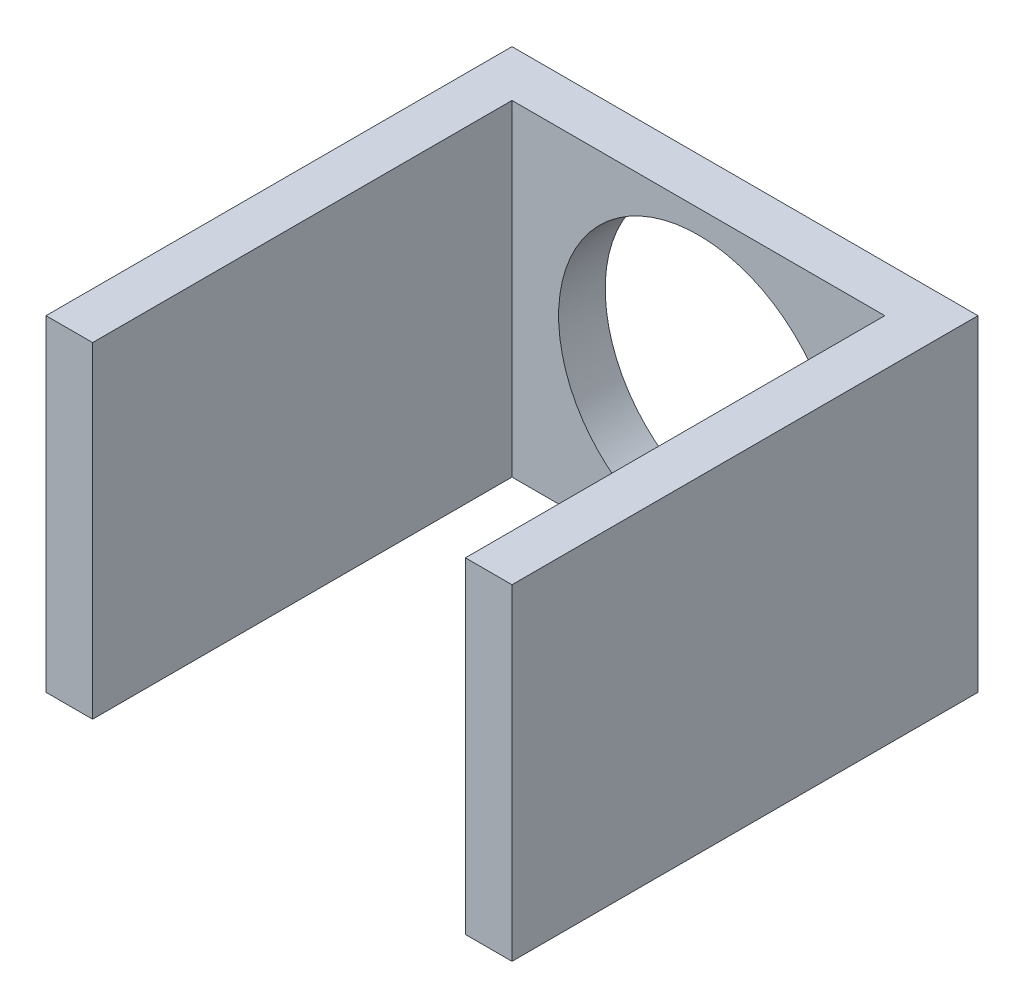
SolidWorks part; units mm, degrees
ref_plane "Plan de face" through (0, 0, 0) normal (0, 0, 1) x (1, 0, 0)
ref_plane "Plan de dessus" through (0, 0, 0) normal (0, 1, 0) x (1, 0, 0)
ref_plane "Plan de droite" through (0, 0, 0) normal (1, 0, 0) x (0, 0, -1)
sketch "Esquisse1" plane through (0, 0, 0) normal (0, 0, 1) x (1, 0, 0)
  line L0 (-90, 70) -> (-90, 0)
  line L1 (0, 0) -> (-100, 0)
  line L2 (0, 0) -> (0, 70)
  line L3 (0, 70) -> (-100, 70)
  line L4 (-100, 0) -> (-100, 70)
  line L5 (-10, 70) -> (-10, 0)
  dimension "D1" = 10
  dimension "D2" = 10
  dimension "D3" = 100
  dimension "D4" = 70
sketch "Esquisse4" plane through (0, 0, 0) normal (0, 0, 1) x (1, 0, 0)
  line L0 (-10, 70) -> (-10, 0) construction
  line L1 (-90, 70) -> (-90, 0) construction
  line L2 (0, 70) -> (-100, 70) construction
  line L3 (0, 0) -> (-100, 0) construction
  circle A0 centre (-50, 35) radius 30
  point P0 (-50, 35)
  dimension "D1" = 40
  dimension "D2" = 40
  dimension "D3" = 35
  dimension "D4" = 35
extrude "Boss.-Extru.2" add sketch "Esquisse1" along normal blind 10 contours L5 L3 L0 L1 region at (-50, 35, 0)
extrude "Boss.-Extru.3" add sketch "Esquisse1<4>" along normal blind 100 contours L3 L5 L1 L2 | L4 L1 L0 L3 region at (-95, 35, 0) region at (-5, 35, 0)
sketch "Esquisse1<4>" plane through (0, 0, 0) normal (0, 0, 1) x (1, 0, 0) same geometry as "Esquisse1"
extrude "Enlèv. mat.-Extru.1" cut sketch "Esquisse4" along normal up to surface (10 mm away) up to face at (-50, 35, 10)
